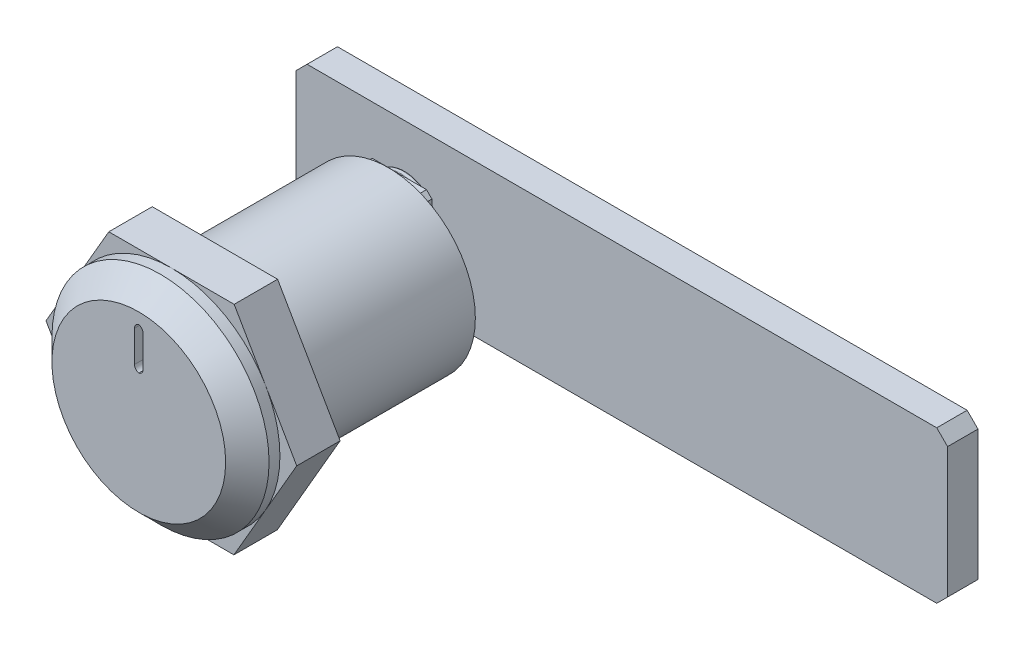
SolidWorks part; units mm, degrees
ref_plane "Front Plane" through (0, 0, 0) normal (0, 0, 1) x (1, 0, 0)
ref_plane "Top Plane" through (0, 0, 0) normal (0, 1, 0) x (1, 0, 0)
ref_plane "Right Plane" through (0, 0, 0) normal (1, 0, 0) x (0, 0, -1)
sketch "Sketch1" plane through (0, 0, 0) normal (0, 0, 1) x (1, 0, 0)
  line L1 (5.7855, 9.9931) -> (-5.7615, 10.0069)
  line L2 (-5.7615, 10.0069) -> (-11.547, 0.0138)
  line L3 (-11.547, 0.0138) -> (-5.7855, -9.9931)
  line L4 (-5.7855, -9.9931) -> (5.7615, -10.0069)
  line L5 (5.7615, -10.0069) -> (11.547, -0.0138)
  line L6 (11.547, -0.0138) -> (5.7855, 9.9931)
  circle A0 centre (0, 0) radius 10 construction
  dimension "D1" = 20
  dimension "D2" = 23.094
extrude "Boss-Extrude1" add sketch "Sketch1" against normal blind 4
sketch "Sketch2" plane through (0, 0, -4) normal (0, 0, -1) x (-1, 0, 0)
  circle A0 centre (0, 0) radius 8
  dimension "D1" = 16
extrude "Boss-Extrude2" add sketch "Sketch2" along normal blind 16
sketch "Sketch3" plane through (0, 0, -20) normal (0, 0, -1) x (-1, 0, 0)
  line L0 (-1, 1.1716) -> (-1, -6.9282)
  line L1 (1, 1.1716) -> (1, -6.9282)
  line L2 (-1, 6.9282) -> (-1, 6.8284)
  line L4 (1, 6.8284) -> (1, 6.9282)
  arc A0 (1, -6.9282) -> (1, 6.9282) centre (0, 0) ccw
  arc A1 (-1, 6.9282) -> (-1, -6.9282) centre (0, 0) ccw
  arc A2 (-1, 6.8284) -> (-1, 1.1716) centre (0, 4) ccw
  arc A3 (1, 1.1716) -> (1, 6.8284) centre (0, 4) ccw
  dimension "D1" = 14
  dimension "D2" = 6
  dimension "D4" = 1
  dimension "D3" = 4
  dimension "D5" = 1
  dimension "D6" = 2
  dimension "D7" = 2
extrude "Cut-Extrude1" cut sketch "Sketch3" against normal blind 16
sketch "Sketch5" plane through (0, 0, 0) normal (0, 0, 1) x (1, 0, 0)
  circle A0 centre (0, 0) radius 10
  dimension "D1" = 20
extrude "Boss-Extrude4" add sketch "Sketch5" along normal blind 3
chamfer "Chamfer2" distance 2 angle 45 1 edges at (10, 0, 3)
sketch "Sketch6" plane through (0, 0, 3) normal (0, 0, 1) x (1, 0, 0)
  line L1 (-0.398, 3.1034) -> (0.398, 3.1034)
  line L2 (-0.398, 3.1034) -> (-0.398, 6.9855)
  line L3 (-0.398, 6.9855) -> (0.398, 6.9855)
  line L4 (0.398, 3.1034) -> (0.398, 6.9855)
  line L5 (-0.398, 3.1034) -> (0.398, 6.9855) construction
  line L6 (-0.398, 6.9855) -> (0.398, 3.1034) construction
  point P0 (0, 5.0444)
extrude "Cut-Extrude2" cut sketch "Sketch6" against normal blind 3
fillet "Fillet2" radius 0.5 4 edges at (0.398, 3.1034, 1.5) (-0.398, 3.1034, 1.5) (0.398, 6.9855, 1.5) (-0.398, 6.9855, 1.5)
sketch "Sketch9" plane through (0, 0, -20) normal (0, 0, -1) x (-1, 0, 0)
  line L1 (-3, 1) -> (3, 1)
  line L2 (-3, 1) -> (-3, 7)
  line L3 (-3, 7) -> (3, 7)
  line L4 (3, 1) -> (3, 7)
  line L5 (-3, 1) -> (3, 7) construction
  line L6 (-3, 7) -> (3, 1) construction
  circle A0 centre (0, 4) radius 2
  point P0 (0, 4)
  dimension "D3" = 4
  dimension "D1" = 6
  dimension "D2" = 6
extrude "Boss-Extrude6" add sketch "Sketch9" along normal blind 1
chamfer "Chamfer3" distance 0.5 angle 45 4 edges at (3, 1, -20.5) (-3, 1, -20.5) (-3, 7, -20.5) (3, 7, -20.5)
sketch "Sketch10" plane through (0, 0, -21) normal (0, 0, -1) x (-1, 0, 0)
  circle A0 centre (0, 4) radius 3
  circle A1 centre (0, 4) radius 2
  dimension "D1" = 6
  dimension "D2" = 4
extrude "Boss-Extrude7" add sketch "Sketch10" along normal blind 0.5 separate body
fillet "Fillet3" radius 0.1 2 edges at (-3, 4, -21) (-3, 4, -21.5)
sketch "Sketch11" plane through (0, 0, -21.5) normal (0, 0, -1) x (-1, 0, 0)
  line L0 (-50, -3) -> (-50, 11)
  line L1 (10, -3) -> (-50, -3)
  line L2 (-50, 11) -> (10, 11)
  line L3 (10, 11) -> (10, -3)
  circle A2 centre (0, 4) radius 2
  circle M6 centre (0, 4) radius 2.9
  dimension "D1" = 10
  dimension "D2" = 60
  dimension "D3" = 7
  dimension "D6" = 4
  dimension "D4" = 14
extrude "Boss-Extrude8" add sketch "Sketch11" along normal blind 2.8 separate body contours M6 region at (20.6495, 4, -21.5)
chamfer "Chamfer4" distance 1 angle 45 4 edges at (-10, -3, -22.9) (50, -3, -22.9) (50, 11, -22.9) (-10, 11, -22.9)
